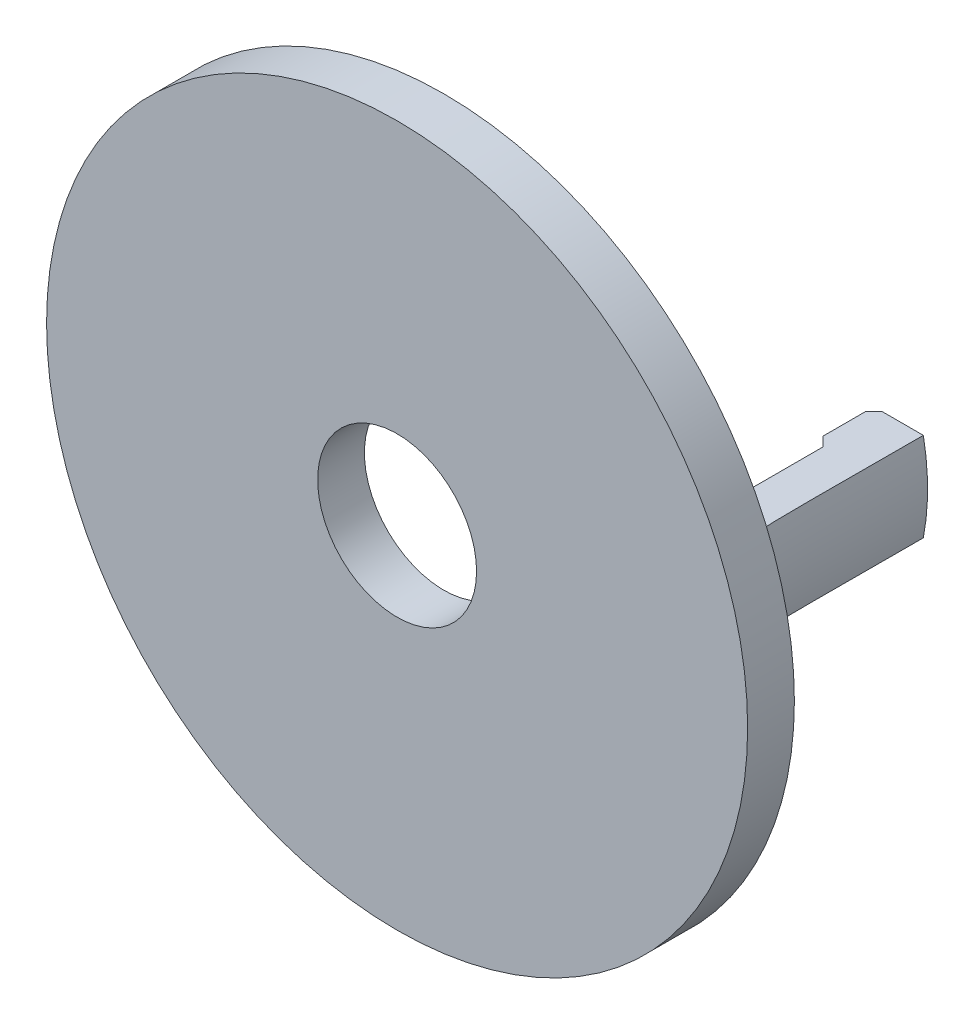
SolidWorks part; units mm, degrees
ref_plane "Front" through (0, 0, 0) normal (0, 0, 1) x (1, 0, 0)
ref_plane "Top" through (0, 0, 0) normal (0, 1, 0) x (1, 0, 0)
ref_plane "Right" through (0, 0, 0) normal (1, 0, 0) x (0, 0, -1)
sketch "Sketch1" plane through (0, 0, 0) normal (0, 0, 1) x (1, 0, 0)
  circle A0 centre (0, 0) radius 26.5
  circle A1 centre (0, 0) radius 37.5
  circle A2 centre (-2, 0) radius 26.5
  dimension "D1" = 53
  dimension "D2" = 75
  dimension "D3" = 2
sketch "Sketch4" plane through (0, 0, 0) normal (0, 0, 1) x (1, 0, 0)
  circle A0 centre (0, 0) radius 37.5
  dimension "D1" = 75
extrude "Boss-Extrude2" add sketch "Sketch4" along normal blind 5
sketch "Sketch5" plane through (0, 0, 5) normal (0, 0, 1) x (1, 0, 0)
  circle A0 centre (0, 0) radius 8.5
  dimension "D1" = 17
extrude "Cut-Extrude1" cut sketch "Sketch5" against normal through all
sketch "Sketch6" plane through (0, 0, 0) normal (0, 1, 0) x (1, 0, 0)
  line L0 (20, 0) -> (26.5, 0) construction
  line L1 (26.5, 0) -> (26.5, 27) construction
  line L2 (17.3536, 0) -> (26.5, 0)
  line L3 (26.5, 27) -> (20, 27) construction
  line L4 (20, 27) -> (18.5, 25.5) construction
  line L5 (18.5, 21) -> (20, 19.5) construction
  line L6 (20, 19.5) -> (20, 0) construction
  line L7 (20.25, 20.3107) -> (20.25, 2.8964)
  line L8 (20, 3) -> (17, 0) construction
  line L9 (20.25, 20.3107) -> (19.25, 21.3107)
  line L10 (18.5, 25.5) -> (18.5, 21) construction
  line L11 (19.25, 21.3107) -> (19.25, 25.8964)
  line L12 (26.5, 0) -> (26.5, 26.75)
  line L13 (17, 0) -> (20, 0) construction
  line L14 (20.25, 2.8964) -> (17.3536, 0)
  line L15 (19.25, 25.8964) -> (20.1036, 26.75)
  line L16 (20.1036, 26.75) -> (26.5, 26.75)
  line L17 (25, 26.5113) -> (25, 41.0721) construction
  line L18 (25, 12.4795) -> (25, 18.7128) construction
  spline S0 degree 3 poles (25, 26.75) (25, 22.7282) (24.9901, 20.5425) (25.0119, 14.9424) (24.7749, 4.9839) (26.5, 0) knots 0 0 0 0 0.446605 0.546605 1 1 1 1
  dimension "D1" = 135
  dimension "D2" = 6.5
  dimension "D3" = 8
  dimension "D4" = 27
  dimension "D5" = 7.5
  dimension "D6" = 0.25
  dimension "D7" = 0.25
  dimension "D8" = 0.25
  dimension "D9" = 0.75
  dimension "D10" = 3
  dimension "D11" = 3
  dimension "D12" = 0.25
  dimension "D13" = 1.5
  dimension "D14" = 0.75
extrude "Boss-Extrude3" add sketch "Sketch6" along normal blind 4.75 and the other way blind 4.75 contours L16 L15 L11 L9 L7 L14 L2 | L12 L16 region at (22.5194, 0, -13.0102) region at (25.7982, 0, -14.9997)
extrude "Cut-Extrude2" cut sketch "Sketch1" against normal through all contours A1 A2 A0 region at (-36.4393, 0, 0)
ref_axis "Axis1" through (0, 0, 0) along (0, 0, -1)
revolve "Cut-Revolve1" cut sketch "Sketch6<4>" angle 360 about axis through (0, 0, 0) along (0, 0, -1) region at (25.7982, 0, -14.9997)
sketch "Sketch6<4>" plane through (0, 0, 0) normal (0, 1, 0) x (1, 0, 0) same geometry as "Sketch6"
mirror "Mirror1" about plane through (0, 0, 0) normal (1, 0, 0) of "Boss-Extrude3", "Cut-Extrude2", "Cut-Revolve1"
equation "\"mate_room\"= 0.25"
equation "\"D6@Sketch6\"=\"mate_room\""
equation "\"D8@Sketch6\"=\"mate_room\""
equation "\"D7@Sketch6\"=\"mate_room\""
equation "\"removal_room\"= 0.75"
equation "\"D9@Sketch6\"=\"removal_room\""
equation "\"D12@Sketch6\"=\"mate_room\""
equation "\"D14@Sketch6\"=\"removal_room\""
equation "\"small_inner_axle_diameter\"=17"
equation "\"D1@Sketch5\"=\"small_inner_axle_diameter\""
